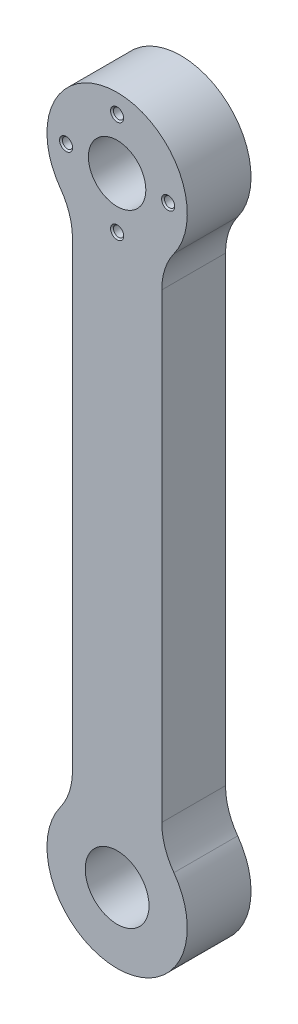
SolidWorks part; units mm, degrees
ref_plane "Plan de face" through (0, 0, 0) normal (0, 0, 1) x (1, 0, 0)
ref_plane "Plan de dessus" through (0, 0, 0) normal (0, 1, 0) x (1, 0, 0)
ref_plane "Plan de droite" through (0, 0, 0) normal (1, 0, 0) x (0, 0, -1)
sketch "Esquisse1" plane through (0, 0, 0) normal (0, 0, 1) x (1, 0, 0)
  line L0 (0, 21.7205) -> (0, -6.0998) construction
  line L1 (-7, 40) -> (-7, -40)
  line L2 (7, 40) -> (7, -40)
  line L3 (-8.714, 0) -> (6.1966, 0) construction
  arc A0 (7, 40) -> (-7, 40) centre (0, 48.4853) ccw
  arc A1 (7, -40) -> (-7, -40) centre (0, -48.4853) cw
  circle A2 centre (0, 48.4853) radius 4.5026
  point P11 (-7, 0)
  dimension "D3" = 11
  dimension "D1" = 80
  dimension "D2" = 14
extrude "Boss.-Extru.1" add sketch "Esquisse1" along normal blind 10
sketch "Esquisse8" plane through (0, 0, 10) normal (0, 0, 1) x (1, 0, 0)
  circle A0 centre (0, 48.4853) radius 8
  arc A1 (7, 40) -> (-7, 40) centre (0, 48.4853) ccw construction
  point P8 (0, 56.4853)
  point P10 (8, 48.4853)
  point P12 (0, 40.4853)
  point P14 (-8, 48.4853)
  dimension "D1" = 16
hole_wizard "Trou taraudé M22" positions "Esquisse8" profile "Esquisse7" tap size "M2" standard "ISO" end condition through all
sketch "Esquisse7" plane through (-8, 48.4853, 10) normal (1, 0, 0) x (0, -1, 0)
  line L0 (0, 0) -> (0, 10)
  line L1 (0, 10) -> (0.8, 10)
  line L2 (0.8, 10) -> (0.8, 0.225)
  line L3 (0.8, 0.225) -> (1.025, 0)
  line L5 (1.025, 0) -> (0, 0)
  line L6 (-0.8, 0.225) -> (-1.025, 0) construction
  line L11 (0, -6.35) -> (0, 107.95) construction
  dimension "Diamètre du trou pour taraudage jusqu'au prochain" = 1.6
  dimension "Profondeur du trou pour taraudage jusqu'au prochain" = 10
  dimension "Diamètre du fraisage entrant" = 2.05
  dimension "Angle du fraisage entrant" = 90
cosmetic thread "Filetage de perçage10" parameters "D2"=2
cosmetic thread "Filetage de perçage11" parameters "D2"=2
cosmetic thread "Filetage de perçage12" parameters "D2"=2
cosmetic thread "Filetage de perçage13" parameters "D2"=2
fillet "Congé1" radius 10 4 edges at (-7, -40, 5) (7, -40, 5) (7, 40, 5) (-7, 40, 5)
sketch "Esquisse9" plane through (0, 0, 10) normal (0, 0, 1) x (1, 0, 0)
  circle A0 centre (0, -48.4853) radius 5
  arc A1 (-8.9048, -42.0273) -> (8.9048, -42.0273) centre (0, -48.4853) ccw construction
  dimension "D1" = 10
extrude "Enlèv. mat.-Extru.1" cut sketch "Esquisse9" against normal blind 10
equation "\"L1\"= 80mm"
equation "\"D1@Esquisse1\"=\"L1\""
